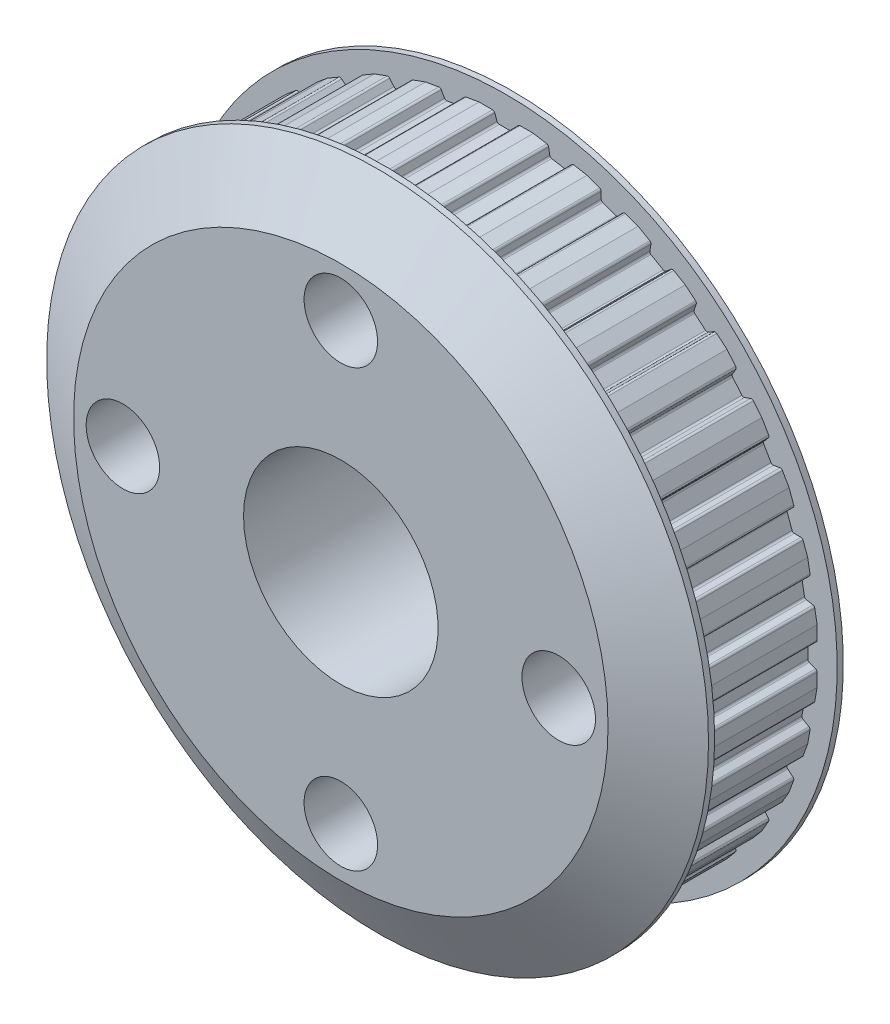
SolidWorks part; units mm, degrees
ref_plane "Front Plane" through (0, 0, 0) normal (0, 0, 1) x (1, 0, 0)
ref_plane "Top Plane" through (0, 0, 0) normal (0, 1, 0) x (1, 0, 0)
ref_plane "Right Plane" through (0, 0, 0) normal (1, 0, 0) x (0, 0, -1)
sketch "Sketch1" plane through (0, 0, 0) normal (0, 0, 1) x (1, 0, 0)
  line L0 (-50.8934, 0.0194) -> (-50.3492, 0.0194)
  line L5 (-50.2596, 0.0821) -> (-50.1666, 0.3377)
  line L6 (-50.0771, 0.4004) -> (-49.4959, 0.4004)
  line L7 (-49.7865, 0.4004) -> (-49.7865, 0) construction
  line L8 (-49.3134, 0.0821) -> (-49.4064, 0.3377)
  line L39 (-51.5116, 0.192) -> (-51.5589, 0.46)
  line L40 (-50.2596, 0.0821) -> (-49.3134, 0.0821) construction
  line L56 (-49.2239, 0.0194) -> (-48.6746, 0.0194)
  line L60 (-52.2084, 0.6381) -> (-51.6361, 0.5372)
  line L61 (-52.4435, 0.3563) -> (-52.3075, 0.592)
  line L62 (-53.0785, 0.4047) -> (-52.5425, 0.3102)
  line L63 (-51.4344, 0.1148) -> (-50.8934, 0.0194)
  line L64 (-53.6574, 0.682) -> (-53.6574, 0.9541)
  line L65 (-54.2661, 1.2424) -> (-53.72, 1.0436)
  line L66 (-54.5466, 1.0057) -> (-54.3717, 1.2141)
  line L67 (-55.1635, 1.1636) -> (-54.6521, 0.9774)
  line L68 (-53.5947, 0.5925) -> (-53.0785, 0.4047)
  line L69 (-55.6854, 1.5372) -> (-55.6382, 1.8052)
  line L70 (-56.1876, 2.1948) -> (-55.6843, 1.9042)
  line L71 (-56.5049, 2.0104) -> (-56.2965, 2.1852)
  line L72 (-57.0851, 2.273) -> (-56.6137, 2.0008)
  line L73 (-55.6392, 1.4382) -> (-55.1635, 1.1636)
  line L74 (-57.5342, 2.7316) -> (-57.4411, 2.9872)
  line L75 (-57.9146, 3.4663) -> (-57.4694, 3.0928)
  line L76 (-58.259, 3.3398) -> (-58.0234, 3.4759)
  line L77 (-58.7848, 3.6992) -> (-58.3679, 3.3494)
  line L78 (-57.5059, 2.626) -> (-57.0851, 2.273)
  line L79 (-59.1474, 4.2288) -> (-59.0114, 4.4644)
  line L80 (-59.3945, 5.0185) -> (-59.0209, 4.5733)
  line L81 (-59.7556, 4.9537) -> (-59.5, 5.0468)
  line L82 (-60.211, 5.3989) -> (-59.8612, 4.982)
  line L83 (-59.1379, 4.12) -> (-58.7848, 3.6992)
  line L84 (-60.4762, 5.9835) -> (-60.3013, 6.1919)
  line L85 (-60.5823, 6.804) -> (-60.2918, 6.3007)
  line L86 (-60.9493, 6.8029) -> (-60.6814, 6.8502)
  line L87 (-61.3204, 7.3205) -> (-61.0483, 6.8491)
  line L88 (-60.4857, 5.8746) -> (-60.211, 5.3989)
  line L89 (-61.48, 7.9422) -> (-61.2716, 8.1171)
  line L90 (-61.4421, 8.7687) -> (-61.2433, 8.2226)
  line L91 (-61.8037, 8.8314) -> (-61.5316, 8.8314)
  line L92 (-62.0793, 9.4055) -> (-61.8932, 8.894)
  line L93 (-61.5083, 7.8366) -> (-61.3204, 7.3205)
  line L94 (-62.1285, 10.0455) -> (-61.8929, 10.1815)
  line L95 (-61.9477, 10.8528) -> (-61.8467, 10.2805)
  line L96 (-62.2928, 10.9773) -> (-62.0249, 10.9301)
  line L97 (-62.4646, 11.5906) -> (-62.3701, 11.0546)
  line L98 (-62.1747, 9.9464) -> (-62.0793, 9.4055)
  line L99 (-62.4019, 12.2294) -> (-62.1463, 12.3224)
  line L100 (-62.0836, 12.9931) -> (-62.0836, 12.4119)
  line L101 (-62.4019, 13.1756) -> (-62.1463, 13.0826)
  line L102 (-62.4646, 13.8094) -> (-62.4646, 13.2652)
  line L103 (-62.4646, 12.1399) -> (-62.4646, 11.5906)
  line L104 (-62.292, 14.4276) -> (-62.024, 14.4749)
  line L105 (-61.8459, 15.1244) -> (-61.9468, 14.5521)
  line L106 (-62.1277, 15.3595) -> (-61.892, 15.2235)
  line L107 (-62.0793, 15.9945) -> (-62.1738, 15.4585)
  line L108 (-62.3692, 14.3504) -> (-62.4646, 13.8094)
  line L109 (-61.802, 16.5734) -> (-61.5299, 16.5734)
  line L110 (-61.2416, 17.1821) -> (-61.4404, 16.636)
  line L111 (-61.4783, 17.4626) -> (-61.2699, 17.2877)
  line L112 (-61.3204, 18.0795) -> (-61.5066, 17.5681)
  line L113 (-61.8915, 16.5107) -> (-62.0793, 15.9945)
  line L114 (-60.9468, 18.6014) -> (-60.6788, 18.5542)
  line L115 (-60.2892, 19.1036) -> (-60.5798, 18.6003)
  line L116 (-60.4736, 19.4209) -> (-60.2988, 19.2125)
  line L117 (-60.211, 20.0011) -> (-60.4832, 19.5297)
  line L118 (-61.0458, 18.5552) -> (-61.3204, 18.0795)
  line L119 (-59.7524, 20.4502) -> (-59.4968, 20.3571)
  line L120 (-59.0177, 20.8306) -> (-59.3912, 20.3854)
  line L121 (-59.1442, 21.175) -> (-59.0081, 20.9394)
  line L122 (-58.7848, 21.7008) -> (-59.1346, 21.2839)
  line L123 (-59.858, 20.4219) -> (-60.211, 20.0011)
  line L124 (-58.2552, 22.0634) -> (-58.0196, 21.9274)
  line L125 (-57.4655, 22.3105) -> (-57.9107, 21.9369)
  line L126 (-57.5303, 22.6716) -> (-57.4372, 22.416)
  line L127 (-57.0851, 23.127) -> (-57.502, 22.7772)
  line L128 (-58.364, 22.0539) -> (-58.7848, 21.7008)
  line L129 (-56.5005, 23.3922) -> (-56.2921, 23.2173)
  line L130 (-55.68, 23.4983) -> (-56.1833, 23.2078)
  line L131 (-55.6811, 23.8653) -> (-55.6338, 23.5974)
  line L132 (-55.1635, 24.2364) -> (-55.6349, 23.9643)
  line L133 (-56.6094, 23.4017) -> (-57.0851, 23.127)
  line L134 (-54.5418, 24.396) -> (-54.3669, 24.1876)
  line L135 (-53.7153, 24.3581) -> (-54.2614, 24.1593)
  line L136 (-53.6526, 24.7197) -> (-53.6526, 24.4476)
  line L137 (-53.0785, 24.9953) -> (-53.59, 24.8092)
  line L138 (-54.6474, 24.4243) -> (-55.1635, 24.2364)
  line L139 (-52.4385, 25.0445) -> (-52.3025, 24.8089)
  line L140 (-51.6312, 24.8637) -> (-52.2035, 24.7627)
  line L141 (-51.5067, 25.2088) -> (-51.5539, 24.9409)
  line L142 (-50.8934, 25.3806) -> (-51.4294, 25.2861)
  line L143 (-52.5376, 25.0907) -> (-53.0785, 24.9953)
  line L144 (-50.2546, 25.3179) -> (-50.1616, 25.0623)
  line L145 (-49.4909, 24.9996) -> (-50.0721, 24.9996)
  line L146 (-49.3084, 25.3179) -> (-49.4014, 25.0623)
  line L147 (-48.6746, 25.3806) -> (-49.2188, 25.3806)
  line L148 (-50.3441, 25.3806) -> (-50.8934, 25.3806)
  line L149 (-48.0564, 25.208) -> (-48.0091, 24.94)
  line L150 (-47.3596, 24.7619) -> (-47.9319, 24.8628)
  line L151 (-47.1245, 25.0437) -> (-47.2605, 24.808)
  line L152 (-46.4895, 24.9953) -> (-47.0255, 25.0898)
  line L153 (-48.1336, 25.2852) -> (-48.6746, 25.3806)
  line L154 (-45.9106, 24.718) -> (-45.9106, 24.4459)
  line L155 (-45.3019, 24.1576) -> (-45.848, 24.3564)
  line L156 (-45.0214, 24.3943) -> (-45.1963, 24.1859)
  line L157 (-44.4045, 24.2364) -> (-44.9159, 24.4226)
  line L158 (-45.9733, 24.8075) -> (-46.4895, 24.9953)
  line L159 (-43.8826, 23.8628) -> (-43.9298, 23.5948)
  line L160 (-43.3804, 23.2052) -> (-43.8837, 23.4958)
  line L161 (-43.0631, 23.3896) -> (-43.2715, 23.2148)
  line L162 (-42.4829, 23.127) -> (-42.9543, 23.3992)
  line L163 (-43.9288, 23.9618) -> (-44.4045, 24.2364)
  line L164 (-42.0338, 22.6684) -> (-42.1269, 22.4128)
  line L165 (-41.6534, 21.9337) -> (-42.0986, 22.3072)
  line L166 (-41.309, 22.0602) -> (-41.5446, 21.9241)
  line L167 (-40.7832, 21.7008) -> (-41.2001, 22.0506)
  line L168 (-42.0621, 22.774) -> (-42.4829, 23.127)
  line L169 (-40.4206, 21.1712) -> (-40.5566, 20.9356)
  line L170 (-40.1735, 20.3815) -> (-40.5471, 20.8267)
  line L171 (-39.8124, 20.4463) -> (-40.068, 20.3532)
  line L172 (-39.357, 20.0011) -> (-39.7068, 20.418)
  line L173 (-40.4301, 21.28) -> (-40.7832, 21.7008)
  line L174 (-39.0918, 19.4165) -> (-39.2667, 19.2081)
  line L175 (-38.9857, 18.596) -> (-39.2762, 19.0993)
  line L176 (-38.6187, 18.5971) -> (-38.8866, 18.5498)
  line L177 (-38.2476, 18.0795) -> (-38.5197, 18.5509)
  line L178 (-39.0823, 19.5254) -> (-39.357, 20.0011)
  line L179 (-38.088, 17.4578) -> (-38.2964, 17.2829)
  line L180 (-38.1259, 16.6313) -> (-38.3247, 17.1774)
  line L181 (-37.7643, 16.5686) -> (-38.0364, 16.5686)
  line L182 (-37.4887, 15.9945) -> (-37.6748, 16.506)
  line L183 (-38.0597, 17.5634) -> (-38.2476, 18.0795)
  line L184 (-37.4395, 15.3545) -> (-37.6751, 15.2185)
  line L185 (-37.6203, 14.5472) -> (-37.7213, 15.1195)
  line L186 (-37.2752, 14.4227) -> (-37.5431, 14.4699)
  line L187 (-37.1034, 13.8094) -> (-37.1979, 14.3454)
  line L188 (-37.3933, 15.4536) -> (-37.4887, 15.9945)
  line L189 (-37.1661, 13.1706) -> (-37.4217, 13.0776)
  line L190 (-37.4844, 12.4069) -> (-37.4844, 12.9881)
  line L191 (-37.1661, 12.2244) -> (-37.4217, 12.3174)
  line L192 (-37.1034, 11.5906) -> (-37.1034, 12.1348)
  line L193 (-37.1034, 13.2601) -> (-37.1034, 13.8094)
  line L194 (-37.276, 10.9724) -> (-37.544, 10.9251)
  line L195 (-37.7221, 10.2756) -> (-37.6212, 10.8479)
  line L196 (-37.4403, 10.0405) -> (-37.676, 10.1765)
  line L197 (-37.4887, 9.4055) -> (-37.3942, 9.9415)
  line L198 (-37.1988, 11.0496) -> (-37.1034, 11.5906)
  line L199 (-37.766, 8.8266) -> (-38.0381, 8.8266)
  line L200 (-38.3264, 8.2179) -> (-38.1276, 8.764)
  line L201 (-38.0897, 7.9374) -> (-38.2981, 8.1123)
  line L202 (-38.2476, 7.3205) -> (-38.0614, 7.8319)
  line L203 (-37.6765, 8.8893) -> (-37.4887, 9.4055)
  line L204 (-38.6212, 6.7986) -> (-38.8892, 6.8458)
  line L205 (-39.2788, 6.2964) -> (-38.9882, 6.7997)
  line L206 (-39.0944, 5.9791) -> (-39.2692, 6.1875)
  line L207 (-39.357, 5.3989) -> (-39.0848, 5.8703)
  line L208 (-38.5222, 6.8448) -> (-38.2476, 7.3205)
  line L209 (-39.8156, 4.9498) -> (-40.0712, 5.0429)
  line L210 (-40.5503, 4.5694) -> (-40.1768, 5.0146)
  line L211 (-40.4238, 4.225) -> (-40.5599, 4.4606)
  line L212 (-40.7832, 3.6992) -> (-40.4334, 4.1161)
  line L213 (-39.71, 4.9781) -> (-39.357, 5.3989)
  line L214 (-41.3128, 3.3366) -> (-41.5484, 3.4726)
  line L215 (-42.1025, 3.0895) -> (-41.6573, 3.4631)
  line L216 (-42.0377, 2.7284) -> (-42.1308, 2.984)
  line L217 (-42.4829, 2.273) -> (-42.066, 2.6228)
  line L218 (-41.204, 3.3461) -> (-40.7832, 3.6992)
  line L219 (-43.0675, 2.0078) -> (-43.2759, 2.1827)
  line L220 (-43.888, 1.9017) -> (-43.3847, 2.1922)
  line L221 (-43.8869, 1.5347) -> (-43.9342, 1.8026)
  line L222 (-44.4045, 1.1636) -> (-43.9331, 1.4357)
  line L223 (-42.9586, 1.9983) -> (-42.4829, 2.273)
  line L224 (-45.0262, 1.004) -> (-45.2011, 1.2124)
  line L225 (-45.8527, 1.0419) -> (-45.3066, 1.2407)
  line L226 (-45.9154, 0.6803) -> (-45.9154, 0.9524)
  line L227 (-46.4895, 0.4047) -> (-45.978, 0.5908)
  line L228 (-44.9206, 0.9757) -> (-44.4045, 1.1636)
  line L229 (-47.1295, 0.3555) -> (-47.2655, 0.5911)
  line L230 (-47.9368, 0.5363) -> (-47.3645, 0.6373)
  line L231 (-48.0613, 0.1912) -> (-48.0141, 0.4591)
  line L232 (-48.6746, 0.0194) -> (-48.1386, 0.1139)
  line L233 (-47.0304, 0.3093) -> (-46.4895, 0.4047)
  arc A0 (-50.3492, 0.0194) -> (-50.2596, 0.0821) centre (-50.3492, 0.1146) ccw
  arc A1 (-50.1666, 0.3377) -> (-50.0771, 0.4004) centre (-50.0771, 0.3051) cw
  arc A2 (-49.4064, 0.3377) -> (-49.4959, 0.4004) centre (-49.4959, 0.3051) ccw
  arc A3 (-49.2239, 0.0194) -> (-49.3134, 0.0821) centre (-49.2239, 0.1146) cw
  arc A4 (-51.4344, 0.1148) -> (-51.5116, 0.192) centre (-51.4178, 0.2086) cw
  arc A5 (-51.5589, 0.46) -> (-51.6361, 0.5372) centre (-51.6527, 0.4434) ccw
  arc A6 (-52.3075, 0.592) -> (-52.2084, 0.6381) centre (-52.225, 0.5443) cw
  arc A7 (-52.5425, 0.3102) -> (-52.4435, 0.3563) centre (-52.526, 0.404) ccw
  arc A8 (-53.5947, 0.5925) -> (-53.6574, 0.682) centre (-53.5621, 0.682) cw
  arc A9 (-53.6574, 0.9541) -> (-53.72, 1.0436) centre (-53.7526, 0.9541) ccw
  arc A10 (-54.3717, 1.2141) -> (-54.2661, 1.2424) centre (-54.2987, 1.1529) cw
  arc A11 (-54.6521, 0.9774) -> (-54.5466, 1.0057) centre (-54.6195, 1.0669) ccw
  arc A12 (-55.6392, 1.4382) -> (-55.6854, 1.5372) centre (-55.5916, 1.5207) cw
  arc A13 (-55.6382, 1.8052) -> (-55.6843, 1.9042) centre (-55.732, 1.8217) ccw
  arc A14 (-56.2965, 2.1852) -> (-56.1876, 2.1948) centre (-56.2353, 2.1123) cw
  arc A15 (-56.6137, 2.0008) -> (-56.5049, 2.0104) centre (-56.5661, 2.0833) ccw
  arc A16 (-57.5059, 2.626) -> (-57.5342, 2.7316) centre (-57.4446, 2.699) cw
  arc A17 (-57.4411, 2.9872) -> (-57.4694, 3.0928) centre (-57.5306, 3.0198) ccw
  arc A18 (-58.0234, 3.4759) -> (-57.9146, 3.4663) centre (-57.9758, 3.3934) cw
  arc A19 (-58.3679, 3.3494) -> (-58.259, 3.3398) centre (-58.3067, 3.4223) ccw
  arc A20 (-59.1379, 4.12) -> (-59.1474, 4.2288) centre (-59.0649, 4.1812) cw
  arc A21 (-59.0114, 4.4644) -> (-59.0209, 4.5733) centre (-59.0939, 4.5121) ccw
  arc A22 (-59.5, 5.0468) -> (-59.3945, 5.0185) centre (-59.4674, 4.9572) cw
  arc A23 (-59.8612, 4.982) -> (-59.7556, 4.9537) centre (-59.7882, 5.0432) ccw
  arc A24 (-60.4857, 5.8746) -> (-60.4762, 5.9835) centre (-60.4032, 5.9222) cw
  arc A25 (-60.3013, 6.1919) -> (-60.2918, 6.3007) centre (-60.3742, 6.2531) ccw
  arc A26 (-60.6814, 6.8502) -> (-60.5823, 6.804) centre (-60.6648, 6.7564) cw
  arc A27 (-61.0483, 6.8491) -> (-60.9493, 6.8029) centre (-60.9658, 6.8967) ccw
  arc A28 (-61.5083, 7.8366) -> (-61.48, 7.9422) centre (-61.4188, 7.8692) cw
  arc A29 (-61.2716, 8.1171) -> (-61.2433, 8.2226) centre (-61.3328, 8.19) ccw
  arc A30 (-61.5316, 8.8314) -> (-61.4421, 8.7687) centre (-61.5316, 8.7361) cw
  arc A31 (-61.8932, 8.894) -> (-61.8037, 8.8314) centre (-61.8037, 8.9266) ccw
  arc A32 (-62.1747, 9.9464) -> (-62.1285, 10.0455) centre (-62.0809, 9.963) cw
  arc A33 (-61.8929, 10.1815) -> (-61.8467, 10.2805) centre (-61.9405, 10.264) ccw
  arc A34 (-62.0249, 10.9301) -> (-61.9477, 10.8528) centre (-62.0415, 10.8363) cw
  arc A35 (-62.3701, 11.0546) -> (-62.2928, 10.9773) centre (-62.2763, 11.0711) ccw
  arc A36 (-62.4646, 12.1399) -> (-62.4019, 12.2294) centre (-62.3694, 12.1399) cw
  arc A37 (-62.1463, 12.3224) -> (-62.0836, 12.4119) centre (-62.1789, 12.4119) ccw
  arc A38 (-62.1463, 13.0826) -> (-62.0836, 12.9931) centre (-62.1789, 12.9931) cw
  arc A39 (-62.4646, 13.2652) -> (-62.4019, 13.1756) centre (-62.3694, 13.2652) ccw
  arc A40 (-62.3692, 14.3504) -> (-62.292, 14.4276) centre (-62.2754, 14.3338) cw
  arc A41 (-62.024, 14.4749) -> (-61.9468, 14.5521) centre (-62.0406, 14.5687) ccw
  arc A42 (-61.892, 15.2235) -> (-61.8459, 15.1244) centre (-61.9397, 15.141) cw
  arc A43 (-62.1738, 15.4585) -> (-62.1277, 15.3595) centre (-62.08, 15.442) ccw
  arc A44 (-61.8915, 16.5107) -> (-61.802, 16.5734) centre (-61.802, 16.4781) cw
  arc A45 (-61.5299, 16.5734) -> (-61.4404, 16.636) centre (-61.5299, 16.6686) ccw
  arc A46 (-61.2699, 17.2877) -> (-61.2416, 17.1821) centre (-61.3311, 17.2147) cw
  arc A47 (-61.5066, 17.5681) -> (-61.4783, 17.4626) centre (-61.4171, 17.5355) ccw
  arc A48 (-61.0458, 18.5552) -> (-60.9468, 18.6014) centre (-60.9633, 18.5076) cw
  arc A49 (-60.6788, 18.5542) -> (-60.5798, 18.6003) centre (-60.6623, 18.648) ccw
  arc A50 (-60.2988, 19.2125) -> (-60.2892, 19.1036) centre (-60.3717, 19.1513) cw
  arc A51 (-60.4832, 19.5297) -> (-60.4736, 19.4209) centre (-60.4007, 19.4821) ccw
  arc A52 (-59.858, 20.4219) -> (-59.7524, 20.4502) centre (-59.785, 20.3606) cw
  arc A53 (-59.4968, 20.3571) -> (-59.3912, 20.3854) centre (-59.4642, 20.4466) ccw
  arc A54 (-59.0081, 20.9394) -> (-59.0177, 20.8306) centre (-59.0906, 20.8918) cw
  arc A55 (-59.1346, 21.2839) -> (-59.1442, 21.175) centre (-59.0617, 21.2227) ccw
  arc A56 (-58.364, 22.0539) -> (-58.2552, 22.0634) centre (-58.3028, 21.9809) cw
  arc A57 (-58.0196, 21.9274) -> (-57.9107, 21.9369) centre (-57.9719, 22.0099) ccw
  arc A58 (-57.4372, 22.416) -> (-57.4655, 22.3105) centre (-57.5268, 22.3834) cw
  arc A59 (-57.502, 22.7772) -> (-57.5303, 22.6716) centre (-57.4408, 22.7042) ccw
  arc A60 (-56.6094, 23.4017) -> (-56.5005, 23.3922) centre (-56.5618, 23.3192) cw
  arc A61 (-56.2921, 23.2173) -> (-56.1833, 23.2078) centre (-56.2309, 23.2902) ccw
  arc A62 (-55.6338, 23.5974) -> (-55.68, 23.4983) centre (-55.7276, 23.5808) cw
  arc A63 (-55.6349, 23.9643) -> (-55.6811, 23.8653) centre (-55.5873, 23.8818) ccw
  arc A64 (-54.6474, 24.4243) -> (-54.5418, 24.396) centre (-54.6148, 24.3348) cw
  arc A65 (-54.3669, 24.1876) -> (-54.2614, 24.1593) centre (-54.294, 24.2488) ccw
  arc A66 (-53.6526, 24.4476) -> (-53.7153, 24.3581) centre (-53.7479, 24.4476) cw
  arc A67 (-53.59, 24.8092) -> (-53.6526, 24.7197) centre (-53.5574, 24.7197) ccw
  arc A68 (-52.5376, 25.0907) -> (-52.4385, 25.0445) centre (-52.521, 24.9969) cw
  arc A69 (-52.3025, 24.8089) -> (-52.2035, 24.7627) centre (-52.22, 24.8565) ccw
  arc A70 (-51.5539, 24.9409) -> (-51.6312, 24.8637) centre (-51.6477, 24.9575) cw
  arc A71 (-51.4294, 25.2861) -> (-51.5067, 25.2088) centre (-51.4129, 25.1923) ccw
  arc A72 (-50.3441, 25.3806) -> (-50.2546, 25.3179) centre (-50.3441, 25.2854) cw
  arc A73 (-50.1616, 25.0623) -> (-50.0721, 24.9996) centre (-50.0721, 25.0949) ccw
  arc A74 (-49.4014, 25.0623) -> (-49.4909, 24.9996) centre (-49.4909, 25.0949) cw
  arc A75 (-49.2188, 25.3806) -> (-49.3084, 25.3179) centre (-49.2188, 25.2854) ccw
  arc A76 (-48.1336, 25.2852) -> (-48.0564, 25.208) centre (-48.1502, 25.1914) cw
  arc A77 (-48.0091, 24.94) -> (-47.9319, 24.8628) centre (-47.9153, 24.9566) ccw
  arc A78 (-47.2605, 24.808) -> (-47.3596, 24.7619) centre (-47.343, 24.8557) cw
  arc A79 (-47.0255, 25.0898) -> (-47.1245, 25.0437) centre (-47.042, 24.996) ccw
  arc A80 (-45.9733, 24.8075) -> (-45.9106, 24.718) centre (-46.0059, 24.718) cw
  arc A81 (-45.9106, 24.4459) -> (-45.848, 24.3564) centre (-45.8154, 24.4459) ccw
  arc A82 (-45.1963, 24.1859) -> (-45.3019, 24.1576) centre (-45.2693, 24.2471) cw
  arc A83 (-44.9159, 24.4226) -> (-45.0214, 24.3943) centre (-44.9485, 24.3331) ccw
  arc A84 (-43.9288, 23.9618) -> (-43.8826, 23.8628) centre (-43.9764, 23.8793) cw
  arc A85 (-43.9298, 23.5948) -> (-43.8837, 23.4958) centre (-43.836, 23.5783) ccw
  arc A86 (-43.2715, 23.2148) -> (-43.3804, 23.2052) centre (-43.3327, 23.2877) cw
  arc A87 (-42.9543, 23.3992) -> (-43.0631, 23.3896) centre (-43.0019, 23.3167) ccw
  arc A88 (-42.0621, 22.774) -> (-42.0338, 22.6684) centre (-42.1234, 22.701) cw
  arc A89 (-42.1269, 22.4128) -> (-42.0986, 22.3072) centre (-42.0374, 22.3802) ccw
  arc A90 (-41.5446, 21.9241) -> (-41.6534, 21.9337) centre (-41.5922, 22.0066) cw
  arc A91 (-41.2001, 22.0506) -> (-41.309, 22.0602) centre (-41.2613, 21.9777) ccw
  arc A92 (-40.4301, 21.28) -> (-40.4206, 21.1712) centre (-40.5031, 21.2188) cw
  arc A93 (-40.5566, 20.9356) -> (-40.5471, 20.8267) centre (-40.4741, 20.8879) ccw
  arc A94 (-40.068, 20.3532) -> (-40.1735, 20.3815) centre (-40.1006, 20.4428) cw
  arc A95 (-39.7068, 20.418) -> (-39.8124, 20.4463) centre (-39.7798, 20.3568) ccw
  arc A96 (-39.0823, 19.5254) -> (-39.0918, 19.4165) centre (-39.1648, 19.4778) cw
  arc A97 (-39.2667, 19.2081) -> (-39.2762, 19.0993) centre (-39.1938, 19.1469) ccw
  arc A98 (-38.8866, 18.5498) -> (-38.9857, 18.596) centre (-38.9032, 18.6436) cw
  arc A99 (-38.5197, 18.5509) -> (-38.6187, 18.5971) centre (-38.6022, 18.5033) ccw
  arc A100 (-38.0597, 17.5634) -> (-38.088, 17.4578) centre (-38.1492, 17.5308) cw
  arc A101 (-38.2964, 17.2829) -> (-38.3247, 17.1774) centre (-38.2352, 17.21) ccw
  arc A102 (-38.0364, 16.5686) -> (-38.1259, 16.6313) centre (-38.0364, 16.6639) cw
  arc A103 (-37.6748, 16.506) -> (-37.7643, 16.5686) centre (-37.7643, 16.4734) ccw
  arc A104 (-37.3933, 15.4536) -> (-37.4395, 15.3545) centre (-37.4871, 15.437) cw
  arc A105 (-37.6751, 15.2185) -> (-37.7213, 15.1195) centre (-37.6275, 15.136) ccw
  arc A106 (-37.5431, 14.4699) -> (-37.6203, 14.5472) centre (-37.5265, 14.5637) cw
  arc A107 (-37.1979, 14.3454) -> (-37.2752, 14.4227) centre (-37.2917, 14.3289) ccw
  arc A108 (-37.1034, 13.2601) -> (-37.1661, 13.1706) centre (-37.1986, 13.2601) cw
  arc A109 (-37.4217, 13.0776) -> (-37.4844, 12.9881) centre (-37.3891, 12.9881) ccw
  arc A110 (-37.4217, 12.3174) -> (-37.4844, 12.4069) centre (-37.3891, 12.4069) cw
  arc A111 (-37.1034, 12.1348) -> (-37.1661, 12.2244) centre (-37.1986, 12.1348) ccw
  arc A112 (-37.1988, 11.0496) -> (-37.276, 10.9724) centre (-37.2926, 11.0662) cw
  arc A113 (-37.544, 10.9251) -> (-37.6212, 10.8479) centre (-37.5274, 10.8313) ccw
  arc A114 (-37.676, 10.1765) -> (-37.7221, 10.2756) centre (-37.6283, 10.259) cw
  arc A115 (-37.3942, 9.9415) -> (-37.4403, 10.0405) centre (-37.488, 9.958) ccw
  arc A116 (-37.6765, 8.8893) -> (-37.766, 8.8266) centre (-37.766, 8.9219) cw
  arc A117 (-38.0381, 8.8266) -> (-38.1276, 8.764) centre (-38.0381, 8.7314) ccw
  arc A118 (-38.2981, 8.1123) -> (-38.3264, 8.2179) centre (-38.2369, 8.1853) cw
  arc A119 (-38.0614, 7.8319) -> (-38.0897, 7.9374) centre (-38.1509, 7.8645) ccw
  arc A120 (-38.5222, 6.8448) -> (-38.6212, 6.7986) centre (-38.6047, 6.8924) cw
  arc A121 (-38.8892, 6.8458) -> (-38.9882, 6.7997) centre (-38.9057, 6.752) ccw
  arc A122 (-39.2692, 6.1875) -> (-39.2788, 6.2964) centre (-39.1963, 6.2487) cw
  arc A123 (-39.0848, 5.8703) -> (-39.0944, 5.9791) centre (-39.1673, 5.9179) ccw
  arc A124 (-39.71, 4.9781) -> (-39.8156, 4.9498) centre (-39.783, 5.0394) cw
  arc A125 (-40.0712, 5.0429) -> (-40.1768, 5.0146) centre (-40.1038, 4.9534) ccw
  arc A126 (-40.5599, 4.4606) -> (-40.5503, 4.5694) centre (-40.4774, 4.5082) cw
  arc A127 (-40.4334, 4.1161) -> (-40.4238, 4.225) centre (-40.5063, 4.1773) ccw
  arc A128 (-41.204, 3.3461) -> (-41.3128, 3.3366) centre (-41.2652, 3.4191) cw
  arc A129 (-41.5484, 3.4726) -> (-41.6573, 3.4631) centre (-41.5961, 3.3901) ccw
  arc A130 (-42.1308, 2.984) -> (-42.1025, 3.0895) centre (-42.0412, 3.0166) cw
  arc A131 (-42.066, 2.6228) -> (-42.0377, 2.7284) centre (-42.1272, 2.6958) ccw
  arc A132 (-42.9586, 1.9983) -> (-43.0675, 2.0078) centre (-43.0062, 2.0808) cw
  arc A133 (-43.2759, 2.1827) -> (-43.3847, 2.1922) centre (-43.3371, 2.1098) ccw
  arc A134 (-43.9342, 1.8026) -> (-43.888, 1.9017) centre (-43.8404, 1.8192) cw
  arc A135 (-43.9331, 1.4357) -> (-43.8869, 1.5347) centre (-43.9807, 1.5182) ccw
  arc A136 (-44.9206, 0.9757) -> (-45.0262, 1.004) centre (-44.9532, 1.0652) cw
  arc A137 (-45.2011, 1.2124) -> (-45.3066, 1.2407) centre (-45.274, 1.1512) ccw
  arc A138 (-45.9154, 0.9524) -> (-45.8527, 1.0419) centre (-45.8201, 0.9524) cw
  arc A139 (-45.978, 0.5908) -> (-45.9154, 0.6803) centre (-46.0106, 0.6803) ccw
  arc A140 (-47.0304, 0.3093) -> (-47.1295, 0.3555) centre (-47.047, 0.4031) cw
  arc A141 (-47.2655, 0.5911) -> (-47.3645, 0.6373) centre (-47.348, 0.5435) ccw
  arc A142 (-48.0141, 0.4591) -> (-47.9368, 0.5363) centre (-47.9203, 0.4425) cw
  arc A143 (-48.1386, 0.1139) -> (-48.0613, 0.1912) centre (-48.1551, 0.2077) ccw
  point P1 (-50.2945, 0.0366)
  point P2 (-49.784, 12.7)
  point P7 (-49.2785, 0.0366)
  point P26 (0, 0)
  point P570 (-49.784, 12.7)
  dimension "D1" = 0.0953
  dimension "D2" = 36
  dimension "D3" = 40
  dimension "D4" = 1.016
  dimension "D7" = 0.381
sketch "Sketch2" plane through (0, 0, 0) normal (0, 0, 1) x (1, 0, 0)
  point P0 (-49.784, 12.7)
extrude "Boss-Extrude1" add sketch "Sketch1" along normal blind 5
sketch "Sketch3" plane through (0, 0, 5) normal (0, 0, 1) x (1, 0, 0)
  circle A0 centre (-49.784, 12.7) radius 13.5
extrude "Boss-Extrude2" add sketch "Sketch3" along normal blind 1.75
sketch "Sketch4" plane through (0, 0, 0) normal (0, 0, -1) x (-1, 0, 0)
  circle A0 centre (49.784, 12.7) radius 13.5
extrude "Boss-Extrude3" add sketch "Sketch4" along normal blind 1.75
sketch "Sketch6" plane through (0, 0, -1.75) normal (0, 0, -1) x (-1, 0, 0)
  point P0 (49.784, 12.7)
hole_wizard "5/16 (0.3125) Dowel Hole2" positions "Sketch6" profile "Sketch7" hole size "5/16" standard "ANSI Inch" end condition through all
sketch "Sketch7" plane through (-49.784, 12.7, -1.75) normal (1, 0, 0) x (0, 1, 0)
  line L0 (0, 0) -> (0, 8.5)
  line L1 (0, 8.5) -> (3.9687, 8.5)
  line L2 (3.9687, 8.5) -> (3.9687, 0)
  line L5 (3.9687, 0) -> (0, 0)
  line L11 (0, -6.35) -> (0, 107.95) construction
  dimension "Thru Hole Dia." = 7.9375
  dimension "Thru Hole Depth" = 8.5
sketch "Sketch8" plane through (0, 0, -1.75) normal (0, 0, -1) x (-1, 0, 0)
  point P0 (49.784, 3.81)
  point P1 (49.784, 12.7)
  point P5 (49.784, 12.7)
  dimension "D1" = 8.89
hole_wizard "Ø3.0mm Dowel Hole1" positions "Sketch8" profile "Sketch9" hole size "Ø3.0" standard "ANSI Metric" end condition through all
sketch "Sketch9" plane through (-49.784, 3.81, -1.75) normal (1, 0, 0) x (0, 1, 0)
  line L0 (0, 0) -> (0, 8.5)
  line L1 (0, 8.5) -> (1.5, 8.5)
  line L2 (1.5, 8.5) -> (1.5, 0)
  line L5 (1.5, 0) -> (0, 0)
  line L11 (0, -6.35) -> (0, 107.95) construction
  dimension "Thru Hole Dia." = 3
  dimension "Thru Hole Depth" = 8.5
sketch "Sketch10" plane through (0, 0, 0) normal (1, 0, 0) x (0, 0, -1)
  line L0 (1.75, 12.7) -> (-6.75, 12.7)
  line L1 (1.75, -0.8) -> (1.75, 26.2) construction
  line L2 (-6.75, 26.2) -> (-6.75, -0.8) construction
ref_axis "Axis1" through (-49.784, 12.7, 6.75) along (0, 0, -1)
pattern_circular "CirPattern1" count 4 over 360 about axis through (-49.784, 12.7, 6.75) along (0, 0, -1) of "Ø3.0mm Dowel Hole1"
chamfer "Chamfer1" distance 1.5 angle 60 1 edges at (-36.284, 12.7, 6.75) first distance on face at (-36.284, 12.7, 6.75)
chamfer "Chamfer2" distance 1.5 angle 60 1 edges at (-63.284, 12.7, -1.75) first distance on face at (-63.284, 12.7, -1.75)
